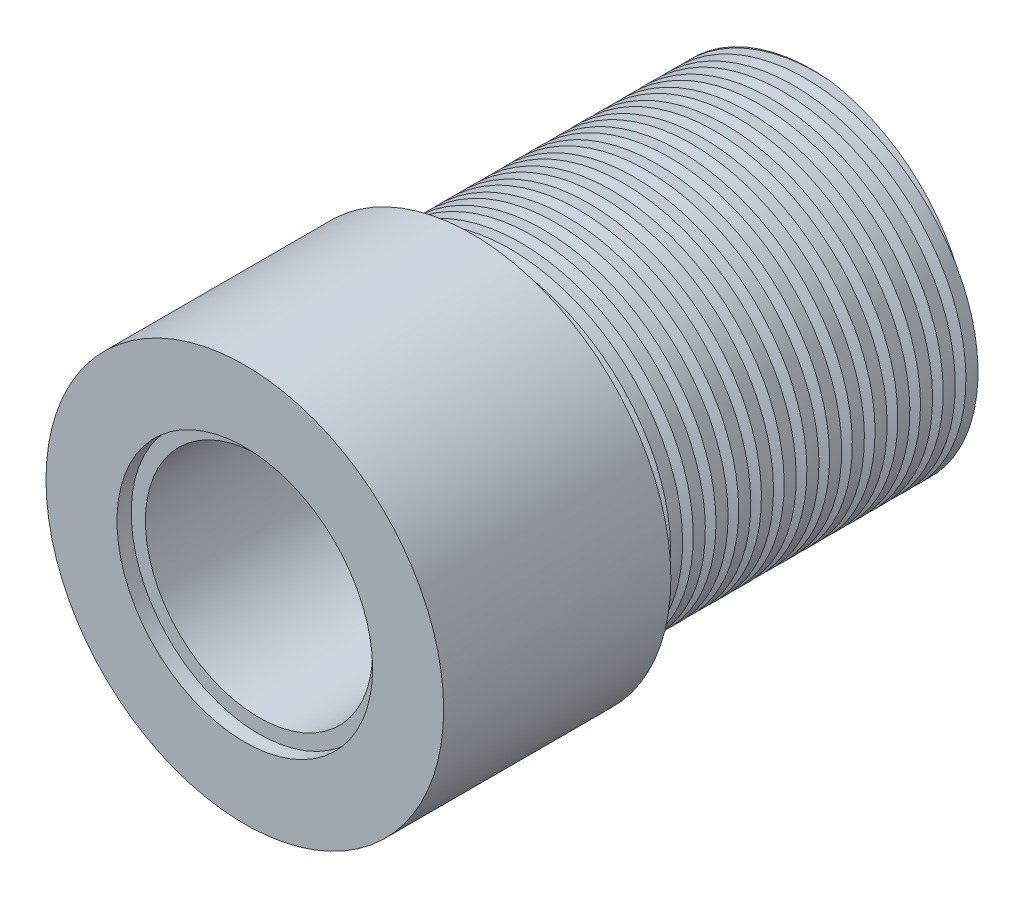
SolidWorks part; units mm, degrees
ref_plane "Front Plane" through (0, 0, 0) normal (0, 0, 1) x (1, 0, 0)
ref_plane "Top Plane" through (0, 0, 0) normal (0, 1, 0) x (1, 0, 0)
ref_plane "Right Plane" through (0, 0, 0) normal (1, 0, 0) x (0, 0, -1)
sketch "Sketch1" plane through (0, 0, 0) normal (0, 0, 1) x (1, 0, 0)
  circle A0 centre (0, 0) radius 6
  dimension "D1" = 12
extrude "Boss-Extrude1" add sketch "Sketch1" along normal blind 12
sketch "Sketch2" plane through (0, 0, 12) normal (0, 0, 1) x (1, 0, 0)
  circle A0 centre (0, 0) radius 7
  dimension "D1" = 14
extrude "Boss-Extrude2" add sketch "Sketch2" along normal blind 8
sketch "Sketch3" plane through (0, 0, 20) normal (0, 0, 1) x (1, 0, 0)
  circle A0 centre (0, 0) radius 4.5
  dimension "D1" = 9
extrude "Cut-Extrude1" cut sketch "Sketch3" against normal blind 0.5
sketch "Sketch4" plane through (0, 0, 0) normal (0, 1, 0) x (1, 0, 0)
  line L0 (5.5, 0) -> (6.5, 0.375)
  line L1 (6, 0) -> (-6, 0) construction
  line L2 (6.5, 0.375) -> (6.5, -0.375)
  line L3 (6.5, -0.375) -> (5.5, 0)
  dimension "D1" = 1
  dimension "D2" = 0.75
  dimension "D3" = 0.375
  dimension "D4" = 5.5
sketch "Sketch5" plane through (0, 0, 0) normal (0, 0, -1) x (-1, 0, 0)
  circle A0 centre (0, 0) radius 6
curve "Helix/Spiral1" pitch 0.8 height 11.6 radius 6 centre (0, 0, 0) axis (0, 0, 1) start towards (1, 0, 0)
sweep "Cut-Sweep1" cut profiles "Sketch4" path "Helix/Spiral1" align with end faces yes
sketch "Sketch6" plane through (0, 0, 19.5) normal (0, 0, 1) x (1, 0, 0)
  circle A0 centre (0, 0) radius 4
  dimension "D1" = 8
extrude "Cut-Extrude2" cut sketch "Sketch6" against normal blind 17
